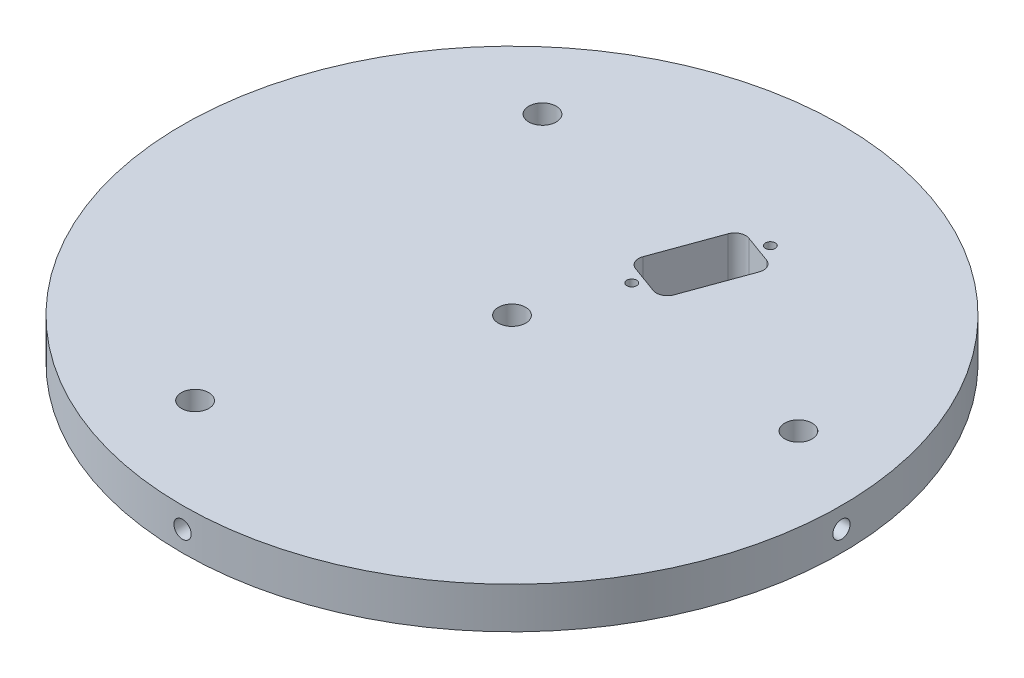
SolidWorks part; units mm, degrees
material "6061-T6 (SS)"
ref_plane "Front Plane" through (0, 0, 0) normal (0, 0, 1) x (1, 0, 0)
ref_plane "Top Plane" through (0, 0, 0) normal (0, 1, 0) x (1, 0, 0)
ref_plane "Right Plane" through (0, 0, 0) normal (1, 0, 0) x (0, 0, -1)
sketch "Sketch1" plane through (0, 0, 0) normal (0, 1, 0) x (1, 0, 0)
  line L0 (0, 0) -> (-50.3682, 60.0265)
  line L1 (0, 0) -> (50.3682, 60.0265)
  line L2 (0, 0) -> (0, 72.1431) construction
  circle A0 centre (0, 0) radius 78.359
  circle A1 centre (0, 0) radius 76.1746
  circle A2 centre (0, 0) radius 76.1746
  dimension "D1" = 156.718
  dimension "D2" = 152.3492
  dimension "D3" = 152.3492
  dimension "D4" = 80
extrude "Boss-Extrude1" add sketch "Sketch1" along normal blind 25.4 contours L2 A2 L1 A0 | L2 A1 L1 A2 | L2 A2 L1 A1 | L2 A0 L1 A2 | A2 L2 A1 L0 | A0 L2 A2 L0 | A2 L2 A0 L0 | A1 L2 A2 L0 region at (0, 0, 13.3592) region at (-23.5316, 0, -29.974) region at (-33.0764, 0, 70.9325) region at (-48.8794, 0, -59.85)
ref_plane "Plane1" through (0, 12.7, 0) normal (0, 1, 0) x (1, 0, 0)
sketch "Sketch6" plane through (0, 25.4, 0) normal (0, 1, 0) x (1, 0, 0)
  circle A0 centre (0, 0) radius 76.1746
  dimension "D1" = 152.3492
extrude "Boss-Extrude5" add sketch "Sketch6" along normal blind 9.525
sketch "Sketch7" plane through (0, 0, 0) normal (0, -1, 0) x (1, 0, 0)
  circle A0 centre (0, 0) radius 76.1746
  dimension "D1" = 152.3492
extrude "Boss-Extrude6" add sketch "Sketch7" along normal blind 9.525
sketch "Sketch8" plane through (0, -9.525, 0) normal (0, -1, 0) x (1, 0, 0)
  circle A0 centre (0, 0) radius 73.025
  dimension "D1" = 146.05
extrude "Cut-Extrude5" cut sketch "Sketch8" against normal up to surface (34.925 mm away) up to face at (0, 25.4, 76.1746)
ref_plane "Plane2" through (0, 0, -76.1746) normal (0, 0, -1) x (-1, 0, 0)
ref_plane "Plane5" through (0, 25.4, 0) normal (0, 1, 0) x (1, 0, 0)
ref_axis "Axis1" through (0, 0, 0) along (0, 1, 0)
sketch "Sketch3" plane through (0, 0, -76.1746) normal (0, 0, -1) x (-1, 0, 0)
  line L4 (76.1746, 0) -> (-76.1746, 0)
  line L5 (-76.1746, -9.525) -> (76.1746, -9.525)
  line L6 (76.1746, 25.4) -> (-76.1746, 25.4)
  line L7 (76.1746, 34.925) -> (-76.1746, 34.925)
  line L8 (0, 34.925) -> (0, 25.4) construction
  line L9 (0, 0) -> (0, -9.525) construction
  circle A0 centre (0, 30.1625) radius 2
  circle A1 centre (0, -4.7625) radius 2
  point P12 (0, 30.1625)
  point P13 (0, -4.7625)
  point P14 (-77.5445, 179.1871)
  dimension "D1" = 4
extrude "Cut-Extrude2" cut sketch "Sketch3" against normal blind 9.525 contours L8 A0 | L8 A0 | L9 A1 | L9 A1 region at (0, 30.1625, -76.1746) region at (0, -4.7625, -76.1746)
extrude "Cut-Extrude3" cut sketch "Sketch1<7>" against normal blind 9.525 from surface contours L2 A1 L1 A2 | A1 L2 A2 L0 | A2 L2 A0 L0 | L2 A2 L1 A0 region at (-23.5316, 0, -29.974) region at (-48.8794, 0, -59.85) starting at plane "Plane5"
sketch "Sketch1<7>" plane through (0, 0, 0) normal (0, 1, 0) x (1, 0, 0) same geometry as "Sketch1"
pattern_circular "CirPattern2" count 3 over 360 about axis through (0, 0, 0) along (0, 1, 0) of "Cut-Extrude3"
ref_plane "Plane3" through (0, 34.925, 0) normal (0, 1, 0) x (1, 0, 0)
sketch "Sketch4" plane through (0, 34.925, 0) normal (0, 1, 0) x (1, 0, 0)
  circle A0 centre (0, 0) radius 73.025
  dimension "D1" = 146.05
extrude "Boss-Extrude4" add sketch "Sketch4" against normal blind 9.525
pattern_circular "CirPattern3" count 4 over 360 about axis through (0, 0, 0) along (0, 1, 0) of "Cut-Extrude2"
sketch "Sketch9" plane through (0, 34.925, 0) normal (0, 1, 0) x (1, 0, 0)
  line L0 (0, 0) -> (-26.8004, -73.6334) construction
  circle A0 centre (0, 0) radius 3.175
  circle A1 centre (-19.5465, -53.7034) radius 3.175
  circle A2 centre (-36.7353, 43.7794) radius 3.175
  circle A3 centre (56.2818, 9.924) radius 3.175
  point P15 (0, 0)
  dimension "D1" = 6.35
  dimension "D2" = 6.35
  dimension "D3" = 57.15
  dimension "D5" = 3
extrude "Cut-Extrude6" cut sketch "Sketch9" against normal through all
sketch "Sketch10" plane through (0, 25.4, 0) normal (0, 1, 0) x (1, 0, 0)
  circle A0 centre (0, 0) radius 82.3228
extrude "Cut-Extrude7" cut sketch "Sketch10" against normal through all
hole_wizard "Tap Drill for #4-40 Tap1" positions "Sketch12" profile "Sketch13" hole size "#4-40" standard "ANSI Inch" end condition through all
sketch "Sketch12" plane through (0, 34.925, 0) normal (0, 1, 0) x (1, 0, 0)
  line L0 (0, 0) -> (18.6243, 51.1699) construction
  line L2 (0, 0) -> (-36.7353, 43.7794) construction
  circle A0 centre (0, 0) radius 21.59 construction
  point P0 (7.3842, 20.288)
  point P2 (15.9347, 43.7803)
  dimension "D3" = 43.18
  dimension "D1" = 60
  dimension "D2" = 25
sketch "Sketch13" plane through (7.3842, 34.925, -20.288) normal (1, 0, 0) x (0, 0, 1)
  line L0 (0, 0) -> (0, 9.525)
  line L1 (0, 9.525) -> (1.1303, 9.525)
  line L2 (1.1303, 9.525) -> (1.1303, 0)
  line L5 (1.1303, 0) -> (0, 0)
  line L11 (0, -6.35) -> (0, 107.95) construction
  dimension "Thru Hole Dia." = 2.2606
  dimension "Thru Hole Depth" = 9.525
sketch "Sketch14" plane through (0, 34.925, 0) normal (0, 1, 0) x (1, 0, 0)
  line L0 (7.3842, 20.288) -> (15.9347, 43.7803) construction
  line L1 (14.6438, 22.7814) -> (19.8932, 37.2038)
  line L2 (11.3883, 21.2633) -> (4.9439, 23.6089)
  line L3 (18.3751, 40.4594) -> (11.9307, 42.8049)
  line L4 (3.4258, 26.8644) -> (8.6751, 41.2868)
  arc A0 (19.8932, 37.2038) -> (18.3751, 40.4594) centre (17.5063, 38.0725) ccw
  arc A1 (11.9307, 42.8049) -> (8.6751, 41.2868) centre (11.0619, 40.4181) ccw
  arc A2 (11.3883, 21.2633) -> (14.6438, 22.7814) centre (12.257, 23.6501) ccw
  arc A3 (4.9439, 23.6089) -> (3.4258, 26.8644) centre (5.8126, 25.9957) cw
  point P0 (8.1661, 22.4361)
  dimension "D4" = 2.54
  dimension "D5" = 2.54
  dimension "D1" = 2.286
  dimension "D2" = 2.286
  dimension "D3" = 11.938
extrude "Cut-Extrude9" cut sketch "Sketch14" against normal through all
equation "\"AB_Coupler_OD_Length\"= 1in"
equation "\"AB_Coupling_Section_Length\"= 0.375in"
equation "\"AB_Coupler_Length\"= \"AB_Coupler_OD_Length\" + \"AB_Coupling_Section_Length\" * 2"
equation "\"Cutout_Angle\" = 80"
equation "\"AB_Coupler_Num_Screws\"= 6"
equation "\"Num_Cutouts\" = 3"
equation "\"AB_Coupler_OD\"= 6.17in"
equation "\"AB_Coupler_ID\"= 5.75in"
equation "\"AB_Coupler_Surface_Diameter\"= 5.998in"
equation "\"D2@Sketch1\"=\"Bodytube_ID\""
equation "\"AB_Coupling_Screw_Diameter\"= 0.1065in"
equation "\"Aft_Section_Length\"= 39in"
equation "\"Aft_Lower_Length\"= 22in"
equation "\"Aft_Upper_Length\"= \"Aft_Section_Length\" - \"Aft_Lower_Length\" - \"AB_Coupler_OD_Length\""
equation "\"Mid_Coupler_Length\"= 13in"
equation "\"Lead_Screw_Dist\" = 2.25in"
equation "\"Lead_Screw_Diam\" = 11mm"
equation "\"Lead_Screw_Length\" = (\"Mid_Coupler_Length\" + 2*0.375in + 2*0.5in)"
equation "\"Bodytube_OD\" = 6.17in"
equation "\"Paddle_Pin_Offset\" = .25in"
equation "\"Bodytube_ID\" = 5.998in"
equation "\"Paddle_Pin_Radius\" = 2.25in"
equation "\"D1@Sketch4\"=\"AB_Coupler_ID\""
equation "\"D1@Sketch6\"=\"AB_Coupler_Surface_Diameter\""
equation "\"D1@Boss-Extrude5\"=\"AB_Coupling_Section_Length\""
equation "\"D1@Sketch7\"=\"AB_Coupler_Surface_Diameter\""
equation "\"D1@Boss-Extrude6\"=\"AB_Coupling_Section_Length\""
equation "\"D1@Sketch8\"=\"AB_Coupler_ID\""
equation "\"D3@Sketch9\"=\"Paddle_Pin_Radius\""
equation "\"Motor_OD\" = 4in"
equation "\"Fwd_Tube_Length\" = 40in"
equation "\"Mid_Tube_Length\" = 1in"
equation "\"AB_Paddle_Height\" = 0.575in"
equation "\"AB_Central_Bushing_Length\" = .75in"
equation "\"Paddle_Gear_OD\" = 3.2in"
equation "\"Fwd_BKHD_From_Top\" = 18in"
equation "\"Fin_Thickness\"= .118in"
equation "\"Guiderail_Cutout_Diameter\"= 1.5in"
equation "\"DB9_Hole_Dist\" = 25mm"
equation "\"D2@Sketch12\"=\"DB9_Hole_Dist\""
equation "\"Drive_Gear_OD\" = 1.7in"
equation "\"D3@Sketch12\"=\"Drive_Gear_OD\""
